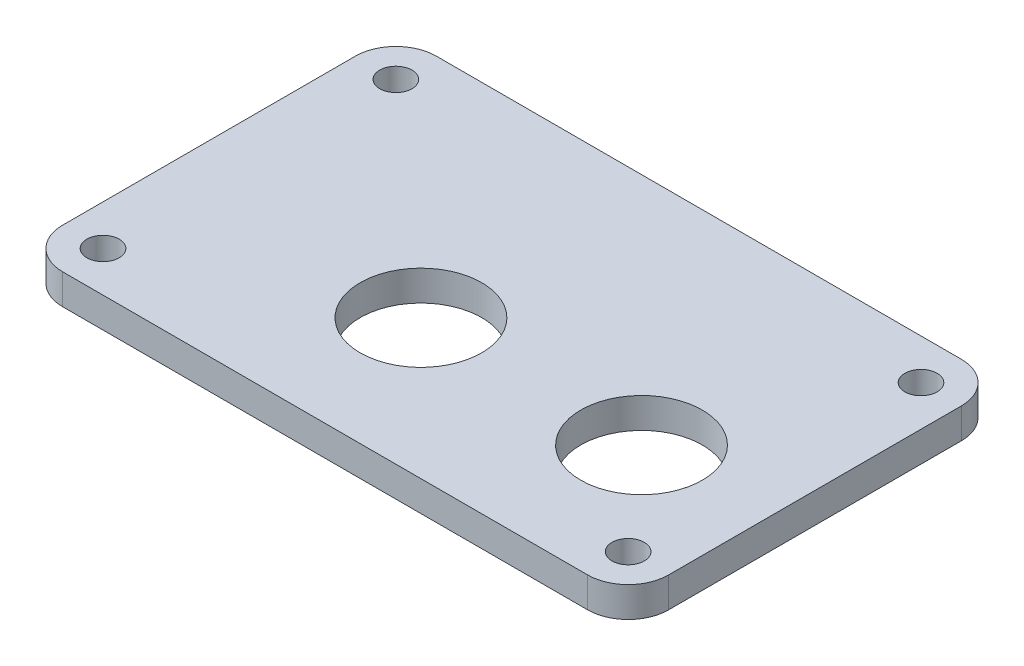
SolidWorks part; units mm, degrees
ref_plane "Front Plane" through (0, 0, 0) normal (0, 0, 1) x (1, 0, 0)
ref_plane "Top Plane" through (0, 0, 0) normal (0, 1, 0) x (1, 0, 0)
ref_plane "Right Plane" through (0, 0, 0) normal (1, 0, 0) x (0, 0, -1)
sketch "Sketch1" plane through (0, 0, 0) normal (0, 1, 0) x (1, 0, 0)
  line L1 (-30, -18.5) -> (30, -18.5)
  line L2 (-30, -18.5) -> (-30, 18.5)
  line L3 (-30, 18.5) -> (30, 18.5)
  line L4 (30, -18.5) -> (30, 18.5)
  line L5 (-30, -18.5) -> (30, 18.5) construction
  line L6 (-30, 18.5) -> (30, -18.5) construction
  point P0 (0, 0)
  dimension "D1" = 37
  dimension "D2" = 60
extrude "Boss-Extrude1" add sketch "Sketch1" along normal blind 2.9972
fillet "Fillet1" radius 4 4 edges at (-30, 1.4986, -18.5) (30, 1.4986, -18.5) (30, 1.4986, 18.5) (-30, 1.4986, 18.5)
sketch "Sketch2" plane through (0, 2.9972, 0) normal (0, 1, 0) x (1, 0, 0)
  circle A0 centre (-26, 14.5) radius 1.6
  circle A1 centre (-26, -14.5) radius 1.6
  circle A2 centre (26, -14.5) radius 1.6
  circle A3 centre (26, 14.5) radius 1.6
  dimension "D1" = 3.2
extrude "Cut-Extrude1" cut sketch "Sketch2" against normal through all
sketch "Sketch3" plane through (0, 2.9972, 0) normal (0, 1, 0) x (1, 0, 0)
  line L0 (-4.318, -4.699) -> (17.526, -4.699) construction
  line L1 (0, 0) -> (17.526, 0) construction
  line L2 (17.526, 0) -> (17.526, -4.699) construction
  line L5 (-4.318, 0) -> (-4.318, -4.699) construction
  line L6 (-4.318, 0) -> (0, 0) construction
  circle A0 centre (-4.318, -4.699) radius 6.0198
  circle A1 centre (17.526, -4.699) radius 6.0198
  dimension "D1" = 12.0396
  dimension "D2" = 17.526
  dimension "D3" = 4.699
  dimension "D4" = 4.318
extrude "Cut-Extrude2" cut sketch "Sketch3" against normal through all
